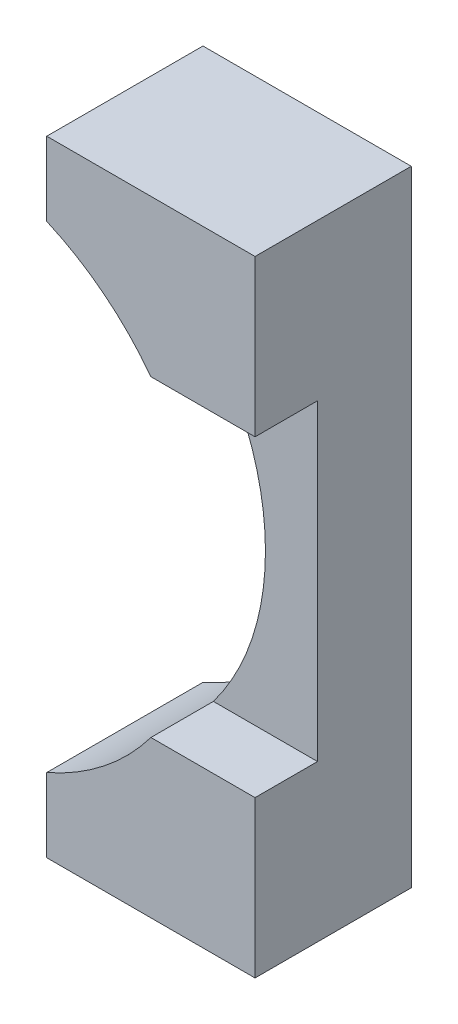
SolidWorks part; units mm, degrees
ref_plane "XY" through (0, 0, 0) normal (0, 0, 1) x (1, 0, 0)
ref_plane "XZ" through (0, 0, 0) normal (0, 1, 0) x (1, 0, 0)
ref_plane "YZ" through (0, 0, 0) normal (1, 0, 0) x (0, 0, -1)
ref_axis "X" through (-1.27, 0, 0) along (1, 0, 0)
ref_axis "Y" through (0, -3.81, 0) along (0, 1, 0)
ref_axis "Z" through (0, 0, 26.67) along (0, 0, -1)
sketch "Sketch1" plane through (0, 0, 0) normal (0, 0, 1) x (1, 0, 0)
  line L1 (0, 0) -> (25.4, 0)
  line L2 (0, 0) -> (0, 76.2)
  line L3 (0, 76.2) -> (25.4, 76.2)
  line L4 (25.4, 0) -> (25.4, 76.2)
  dimension "D1" = 25.4
  dimension "D2" = 76.2
extrude "Boss-Extrude1" add sketch "Sketch1" along normal blind 19.05
sketch "Sketch2" plane through (0, 0, 19.05) normal (0, 0, 1) x (1, 0, 0)
  line L1 (0, 76.2) -> (0, 0) construction
  line L2 (-12.7, 38.1) -> (0, 38.1) construction
  line L3 (0, 76.2) -> (0, 0) construction
  circle A0 centre (-12.7, 38.1) radius 31.75
  point P2 (0, 0)
  dimension "D1" = 63.5
  dimension "D2" = 12.7
extrude "Cut-Extrude1" cut sketch "Sketch2" against normal blind 25.4
sketch "Sketch3" plane through (0, 0, 0) normal (0, 0, -1) x (-1, 0, 0)
  line L0 (-7.62, 76.2) -> (-7.62, 62.4959)
  line L1 (-25.4, 76.2) -> (0, 76.2) construction
  line L6 (0, 67.1994) -> (0, 76.2)
  line L7 (0, 76.2) -> (-25.4, 76.2)
  line L8 (-25.4, 76.2) -> (-25.4, 0)
  line L10 (0, 67.1994) -> (0, 76.2)
  line L11 (0, 76.2) -> (-7.62, 76.2)
  line L14 (-25.4, 0) -> (0, 0)
  line L15 (0, 0) -> (0, 9.0006)
  line L16 (0, 0) -> (0, 9.0006)
  arc A0 (0, 67.1994) -> (0, 9.0006) centre (12.7, 38.1) ccw construction
  arc A2 (0, 67.1994) -> (0, 9.0006) centre (12.7, 38.1) ccw
  arc A3 (0, 67.1994) -> (-7.62, 62.4959) centre (12.7, 38.1) ccw
  point P7 (0, 71.6997)
  dimension "D2" = 7.62
  dimension "D1" = 0
sketch "Sketch4" plane through (25.4, 0, 0) normal (1, 0, 0) x (0, 0, -1)
  line L0 (-19.05, 0) -> (-19.05, 76.2) construction
  line L1 (-19.05, 57.15) -> (-11.43, 57.15)
  line L2 (-19.05, 57.15) -> (-19.05, 19.05)
  line L3 (-19.05, 19.05) -> (-11.43, 19.05)
  line L4 (-11.43, 57.15) -> (-11.43, 19.05)
  line L5 (-11.43, 38.1) -> (0, 38.1) construction
  line L6 (0, 0) -> (0, 76.2) construction
  dimension "D1" = 7.62
  dimension "D2" = 38.1
extrude "Cut-Extrude3" cut sketch "Sketch4" against normal through all
